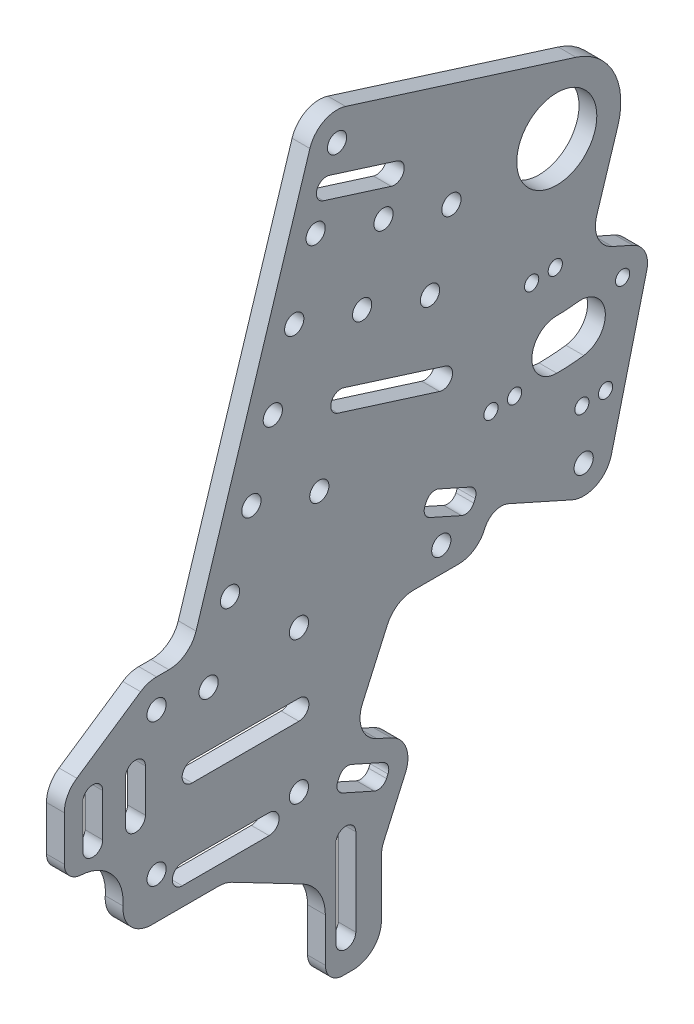
SolidWorks part; units mm, degrees
ref_plane "Front Plane" through (0, 0, 0) normal (0, 0, 1) x (1, 0, 0)
ref_plane "Top Plane" through (0, 0, 0) normal (0, 1, 0) x (1, 0, 0)
ref_plane "Right Plane" through (0, 0, 0) normal (1, 0, 0) x (0, 0, -1)
sketch "Sketch2" plane through (0, 0, 0) normal (1, 0, 0) x (0, 0, -1)
  line L3 (55, 0) -> (-55, 0) construction
  line L9 (71.2451, 111.4062) -> (68.2175, 112.7608) construction
  line L28 (0, 0) -> (-57.2178, 40.0643) construction
  line L40 (0, 0) -> (113.3671, 198.5091) construction
  line L41 (113.3671, 198.5091) -> (58.7631, 215.7257) construction
  line L42 (99.338, 182.3162) -> (24.13, 14.224) construction
  line L43 (35.7423, 40.1778) -> (35.2236, 39.0185) construction
  line L44 (30.078, 221.0415) -> (54.3024, 213.4035)
  line L45 (32.2166, 227.8243) -> (56.441, 220.1864)
  line L46 (40.1245, 41.8508) -> (51.4581, 36.7799)
  line L47 (53.1311, 32.3976) -> (52.6124, 31.2384)
  line L48 (48.2302, 29.5654) -> (36.8966, 34.6363)
  line L49 (104.399, 158.5001) -> (136.8581, 143.9772) construction
  line L50 (136.8581, 143.9772) -> (122.3352, 111.518) construction
  line L51 (112.8406, 159.0638) -> (145.2997, 144.5408) construction
  line L52 (66.8628, 109.7332) -> (66.3442, 108.5739)
  line L53 (71.2451, 111.4062) -> (82.5787, 106.3353)
  line L54 (84.2517, 101.953) -> (83.733, 100.7938)
  line L55 (79.3508, 99.1208) -> (68.0172, 104.1917)
  line L56 (43.9148, 180.4584) -> (36.2769, 156.2339) construction
  line L57 (-29.4365, 93.5262) -> (-29.4365, 42.7262) construction
  line L61 (122.3352, 111.518) -> (89.876, 126.041) construction
  line L62 (89.876, 126.041) -> (104.399, 158.5001) construction
  line L63 (104.399, 158.5001) -> (122.3352, 111.518) construction
  line L65 (145.2997, 144.5408) -> (130.7768, 112.0817) construction
  line L66 (130.7768, 112.0817) -> (98.3176, 126.6046) construction
  line L67 (98.3176, 126.6046) -> (112.8406, 159.0638) construction
  line L68 (112.8406, 159.0638) -> (130.7768, 112.0817) construction
  line L69 (58.7631, 215.7257) -> (31.1473, 224.4329) construction
  line L70 (40.1245, 41.8508) -> (37.0969, 43.2054) construction
  line L71 (38.1, 20.2565) -> (38.1, -10.7315) construction
  line L72 (41.656, 20.2565) -> (41.656, -10.7315)
  line L73 (34.544, 20.2565) -> (34.544, -10.7315)
  line L74 (0, -14.2875) -> (38.1, -14.2875) construction
  line L75 (-20.2565, 38.1) -> (10.7315, 38.1) construction
  line L76 (-20.2565, 41.656) -> (10.7315, 41.656)
  line L77 (-20.2565, 34.544) -> (10.7315, 34.544)
  line L78 (14.2875, 38.1) -> (14.2875, 0) construction
  line L79 (-52.2013, 78.1643) -> (-52.2013, 62.9243) construction
  line L80 (-48.6453, 78.1643) -> (-48.6453, 62.9243)
  line L81 (-55.7573, 78.1643) -> (-55.7573, 62.9243)
  line L82 (-36.9613, 78.1643) -> (-36.9613, 62.9243) construction
  line L83 (-33.4053, 78.1643) -> (-33.4053, 62.9243)
  line L84 (-40.5173, 78.1643) -> (-40.5173, 62.9243)
  line L85 (31.1473, 224.4329) -> (-10.8613, 91.1986) construction
  line L86 (31.1473, 224.4329) -> (34.9663, 236.5451) construction
  line L87 (35.7423, 40.1778) -> (35.2236, 39.0185)
  line L92 (27.3284, 212.3207) -> (75.7772, 197.0448) construction
  line L93 (19.6904, 188.0963) -> (68.1392, 172.8204) construction
  line L94 (36.2769, 156.2339) -> (12.0525, 163.8719) construction
  line L95 (36.2769, 156.2339) -> (72.6135, 144.777) construction
  line L96 (37.3462, 159.6254) -> (73.6828, 148.1685)
  line L97 (35.2076, 152.8425) -> (71.5442, 141.3856)
  line L98 (36.2769, 156.2339) -> (28.639, 132.0095) construction
  line L99 (28.639, 132.0095) -> (4.4146, 139.6475) construction
  line L100 (-29.4365, 68.1262) -> (-16.7365, 68.1262) construction
  line L101 (-16.7365, 68.1262) -> (21.3635, 68.1262) construction
  line L102 (-16.7365, 71.6822) -> (21.3635, 71.6822)
  line L103 (-16.7365, 64.5702) -> (21.3635, 64.5702)
  line L104 (38.0214, 246.2349) -> (120.2412, 220.3111)
  line L105 (25.2765, 239.6003) -> (-15.3369, 110.7911)
  line L106 (-29.4365, 103.6862) -> (-25.0266, 103.6862)
  line L107 (-35.1197, 101.9481) -> (-57.8844, 86.5862)
  line L108 (-62.3613, 62.2565) -> (-62.3613, 78.1643)
  line L109 (-31.257, 27.94) -> (-7.2528, 27.94)
  line L110 (30.7975, -15.5575) -> (30.7975, 0)
  line L113 (135.1691, 191.635) -> (127.6222, 167.6992)
  line L114 (133.1625, 155.37) -> (140.4889, 152.092)
  line L115 (145.4838, 141.8254) -> (132.8214, 91.067)
  line L116 (118.8141, 84.2522) -> (96.1696, 94.3838)
  line L117 (50.8, 8.2625) -> (50.8, -11.7475)
  line L118 (37.1475, -21.9075) -> (40.64, -21.9075)
  line L120 (54.2529, 43.0263) -> (49.1657, 45.3024)
  line L121 (52.9447, 78.6256) -> (44.0411, 58.7259)
  line L122 (59.3776, 29.6029) -> (51.6859, 12.4119)
  line L123 (62.2187, 84.6362) -> (78.2669, 84.6362)
  line L124 (87.7799, 91.1809) -> (87.541, 90.6468)
  line L125 (30.7975, 0) -> (15.3035, 0) construction
  line L126 (22.4684, 13.7378) -> (-2.5545, 26.7884)
  line L127 (0, 0) -> (0, 15.494) construction
  circle A36 centre (0, 0) radius 14.2875 construction
  circle A37 centre (-57.2178, 40.0643) radius 14.2875 construction
  circle A38 centre (113.3671, 198.5091) radius 14.2875
  arc A39 (54.3024, 213.4035) -> (56.441, 220.1864) centre (55.3717, 216.795) ccw
  arc A40 (32.2166, 227.8243) -> (30.078, 221.0415) centre (31.1473, 224.4329) ccw
  arc A41 (51.4581, 36.7799) -> (53.1311, 32.3976) centre (50.1035, 33.7523) cw
  arc A42 (52.6124, 31.2384) -> (48.2302, 29.5654) centre (49.5848, 32.593) cw
  arc A43 (36.8966, 34.6363) -> (35.2236, 39.0185) centre (38.2512, 37.6639) cw
  arc A44 (35.7423, 40.1778) -> (40.1245, 41.8508) centre (38.7699, 38.8232) cw
  arc A45 (79.3508, 99.1208) -> (83.733, 100.7938) centre (80.7054, 102.1484) ccw
  arc A46 (84.2517, 101.953) -> (82.5787, 106.3353) centre (81.2241, 103.3077) ccw
  arc A47 (68.0172, 104.1917) -> (66.3442, 108.5739) centre (69.3718, 107.2193) cw
  arc A48 (66.8628, 109.7332) -> (71.2451, 111.4062) centre (69.8905, 108.3785) cw
  circle A49 centre (-29.4365, 42.7262) radius 3.429
  circle A50 centre (21.3635, 93.5262) radius 3.429
  circle A51 centre (122.9635, 93.5262) radius 3.429
  circle A54 centre (104.399, 158.5001) radius 2.54
  circle A55 centre (136.8581, 143.9772) radius 2.54
  circle A56 centre (122.3352, 111.518) radius 2.54
  circle A57 centre (89.876, 126.041) radius 2.54
  arc A60 (113.3671, 135.0091) -> (121.8087, 135.5727) centre (113.3671, 198.5091) ccw construction
  circle A61 centre (112.8406, 159.0638) radius 2.54
  circle A62 centre (130.7768, 112.0817) radius 2.54
  circle A63 centre (98.3176, 126.6046) radius 2.54
  circle A64 centre (-29.4365, 93.5262) radius 3.429
  circle A65 centre (21.3635, 42.7262) radius 3.429
  circle A66 centre (72.1635, 93.5262) radius 3.429
  arc A67 (41.656, 20.2565) -> (34.544, 20.2565) centre (38.1, 20.2565) ccw
  arc A68 (34.544, -10.7315) -> (41.656, -10.7315) centre (38.1, -10.7315) ccw
  arc A69 (-20.2565, 41.656) -> (-20.2565, 34.544) centre (-20.2565, 38.1) ccw
  arc A70 (10.7315, 34.544) -> (10.7315, 41.656) centre (10.7315, 38.1) ccw
  arc A71 (-48.6453, 78.1643) -> (-55.7573, 78.1643) centre (-52.2013, 78.1643) ccw
  arc A72 (-55.7573, 62.9243) -> (-48.6453, 62.9243) centre (-52.2013, 62.9243) ccw
  arc A73 (-33.4053, 78.1643) -> (-40.5173, 78.1643) centre (-36.9613, 78.1643) ccw
  arc A74 (-40.5173, 62.9243) -> (-33.4053, 62.9243) centre (-36.9613, 62.9243) ccw
  circle A75 centre (34.9663, 236.5451) radius 3.429
  circle A76 centre (27.3284, 212.3207) radius 3.429
  circle A77 centre (19.6904, 188.0963) radius 3.429
  circle A78 centre (12.0525, 163.8719) radius 3.429
  circle A79 centre (4.4146, 139.6475) radius 3.429
  circle A80 centre (-3.2234, 115.423) radius 3.429
  circle A81 centre (-10.8613, 91.1986) radius 3.429
  circle A82 centre (51.5528, 204.6828) radius 3.429
  circle A83 centre (43.9148, 180.4584) radius 3.429
  circle A84 centre (75.7772, 197.0448) radius 3.429
  circle A85 centre (68.1392, 172.8204) radius 3.429
  arc A86 (37.3462, 159.6254) -> (35.2076, 152.8425) centre (36.2769, 156.2339) ccw
  arc A87 (71.5442, 141.3856) -> (73.6828, 148.1685) centre (72.6135, 144.777) ccw
  circle A88 centre (28.639, 132.0095) radius 3.429
  arc A89 (-16.7365, 71.6822) -> (-16.7365, 64.5702) centre (-16.7365, 68.1262) ccw
  arc A90 (21.3635, 64.5702) -> (21.3635, 71.6822) centre (21.3635, 68.1262) ccw
  arc A91 (38.0214, 246.2349) -> (25.2765, 239.6003) centre (34.9663, 236.5451) ccw
  arc A92 (120.2412, 220.3111) -> (135.1691, 191.635) centre (113.3671, 198.5091) cw
  arc A93 (-35.1197, 101.9481) -> (-29.4365, 103.6862) centre (-29.4365, 93.5262) cw
  arc A94 (-62.3613, 78.1643) -> (-57.8844, 86.5862) centre (-52.2013, 78.1643) cw
  arc A95 (-25.0266, 103.6862) -> (-15.3369, 110.7911) centre (-25.0266, 113.8462) ccw
  arc A96 (-56.356, 55.9159) -> (-62.3613, 62.2565) centre (-56.0113, 62.2565) cw
  arc A97 (-41.388, 38.8666) -> (-56.356, 55.9159) centre (-57.2178, 40.0643) ccw
  arc A99 (-31.257, 27.94) -> (-41.388, 38.8666) centre (-31.257, 38.1) cw
  arc A100 (37.1475, -21.9075) -> (30.7975, -15.5575) centre (37.1475, -15.5575) cw
  arc A101 (140.4889, 152.092) -> (145.4838, 141.8254) centre (136.8581, 143.9772) cw
  arc A102 (132.8214, 91.067) -> (118.8141, 84.2522) centre (122.9635, 93.5262) cw
  arc A105 (133.1625, 155.37) -> (127.6222, 167.6992) centre (137.3119, 164.644) cw
  arc A106 (121.8087, 135.5727) -> (113.3671, 135.0091) centre (113.3671, 198.5091) cw construction
  arc A107 (113.3671, 126.1191) -> (122.9905, 126.7616) centre (113.3671, 198.5091) ccw
  arc A108 (113.3671, 143.8991) -> (120.6269, 144.3838) centre (113.3671, 198.5091) ccw
  arc A109 (113.3671, 143.8991) -> (113.3671, 126.1191) centre (113.3671, 135.0091) ccw
  arc A110 (122.9905, 126.7616) -> (120.6269, 144.3838) centre (121.8087, 135.5727) ccw
  arc A111 (40.64, -21.9075) -> (50.8, -11.7475) centre (40.64, -11.7475) ccw
  arc A112 (50.8, 8.2625) -> (51.6859, 12.4119) centre (60.96, 8.2625) cw
  arc A113 (54.2529, 43.0263) -> (59.3776, 29.6029) centre (50.1035, 33.7523) cw
  arc A114 (49.1657, 45.3024) -> (44.0411, 58.7259) centre (53.3151, 54.5765) cw
  arc A115 (62.2187, 84.6362) -> (52.9447, 78.6256) centre (62.2187, 74.4762) ccw
  arc A117 (78.2669, 84.6362) -> (87.541, 90.6468) centre (78.2669, 94.7962) ccw
  arc A118 (87.7799, 91.1809) -> (96.1696, 94.3838) centre (93.5762, 88.5875) cw
  arc A121 (30.7975, 0) -> (22.4684, 13.7378) centre (15.3035, 0) ccw
  arc A122 (-7.2528, 27.94) -> (-2.5545, 26.7884) centre (-7.2528, 17.78) cw
  point P31 (113.3671, 135.0091)
  point P37 (2.3135, 68.1262)
  point P70 (54.4452, 150.5055)
  point P80 (121.8087, 135.5727)
  point P89 (38.1, 4.7625)
  point P98 (-4.7625, 38.1)
  point P100 (38.1, 23.8125)
  point P109 (-23.8125, 38.1)
  point P111 (-52.2013, 70.5443)
  point P116 (-36.9613, 70.5443)
  point P176 (117.5973, 135.1502)
  point P179 (-4.7625, 27.94)
  point P201 (63.527, 38.8769)
  point P204 (39.8917, 49.4518)
  dimension "D1" = 28.575
  dimension "D2" = 69.85
  dimension "D5" = 25.4
  dimension "D6" = 3.556
  dimension "D7" = 184.15
  dimension "D8" = 28.0103
  dimension "D9" = 3.3168
  dimension "D10" = 10.16
  dimension "D11" = 27.7812
  dimension "D13" = 6.858
  dimension "D15" = 53.4619
  dimension "D17" = 180.1812
  dimension "D18" = 53.4619
  dimension "D19" = 3.556
  dimension "D20" = 38.1
  dimension "D21" = 38.1
  dimension "D24" = 5.08
  dimension "D28" = 10.16
  dimension "D30" = 35.56
  dimension "D31" = 8.4416
  dimension "D33" = 65.895
  dimension "D34" = 35
  dimension "D35" = 60.27
  dimension "D40" = 76.2
  dimension "D16" = 10.16
  dimension "D27" = 10.16
  dimension "D47" = 38.1
  dimension "D48" = 7.112
  dimension "D50" = 38.1
  dimension "D53" = 3.556
  dimension "D56" = 12.7
  dimension "D57" = 12.7
  dimension "D58" = 25.4
  dimension "D60" = 25.4
  dimension "D61" = 25.4
  dimension "D25" = 3.556
  dimension "D63" = 6.35
  dimension "D64" = 31.75
  dimension "D65" = 10.16
  dimension "D69" = 16.51
  dimension "D70" = 12.7
  dimension "D73" = 6.35
  dimension "D74" = 8.89
  dimension "D72" = 8.89
  dimension "D75" = 8.89
  dimension "D77" = 7.2813
  dimension "D78" = 15.494
  dimension "D81" = 15.494
  dimension "D82" = 10.16
  dimension "D83" = 6.35
  dimension "D3" = 228.6
  dimension "D12" = 2.6619
  dimension "D14" = 78.5812
  dimension "D22" = 35.56
  dimension "D23" = 63.5
  dimension "D26" = 12.7
  dimension "D29" = 8.4667
  dimension "D32" = 50.8
  dimension "D36" = 16.1929
  dimension "D37" = 12.4163
  dimension "D38" = 1.27
  dimension "D39" = 76.2
  dimension "D41" = 1.27
  dimension "D42" = 12.4163
  dimension "D43" = 17.5
  dimension "D44" = 7.112
  dimension "D45" = 3.556
  dimension "D46" = 38.1
  dimension "D49" = 38.1
  dimension "D51" = 15.24
  dimension "D52" = 15.24
  dimension "D54" = 38.1
  dimension "D55" = 23.8125
  dimension "D59" = 25.4
  dimension "D62" = 25.4
  dimension "D66" = 15.494
  dimension "D67" = 3
  dimension "D68" = 25.4
  dimension "D71" = 7.62
  dimension "D76" = 60.8098
  dimension "D79" = 10.16
  dimension "D80" = 7.62
extrude "Boss-Extrude1" add sketch "Sketch2" along normal blind 3.175 and the other way blind 3.175
